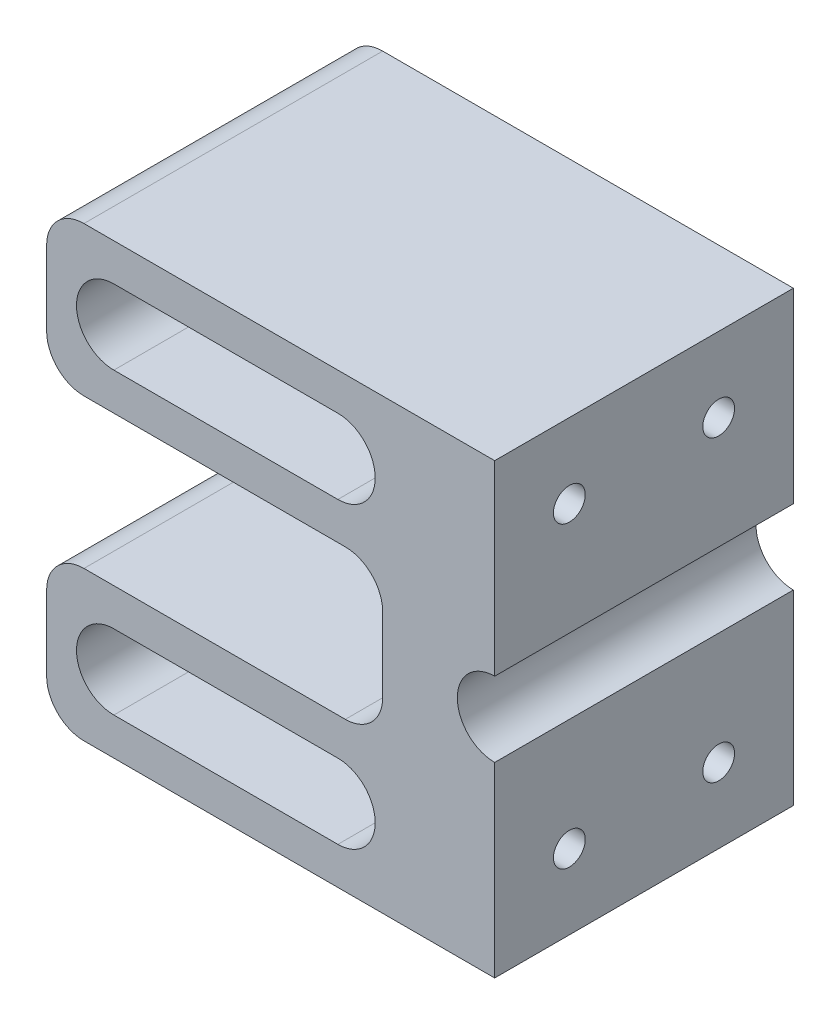
SolidWorks part; units mm, degrees
note: '?' marks a value the reader was unsure of.
ref_plane "Front Plane" through (0, 0, 0) normal (0, 0, 1) x (1, 0, 0)
ref_plane "Top Plane" through (0, 0, 0) normal (0, 1, 0) x (1, 0, 0)
ref_plane "Right Plane" through (0, 0, 0) normal (1, 0, 0) x (0, 0, -1)
sketch "Sketch1" plane through (0, 0, 0) normal (0, 0, 1) x (1, 0, 0)
  line L1 (-19.05, -12.7) -> (19.05, -12.7)
  line L2 (-19.05, -12.7) -> (-19.05, 12.7)
  line L3 (-19.05, 12.7) -> (19.05, 12.7)
  line L4 (19.05, -12.7) -> (19.05, 12.7)
  line L5 (-19.05, -12.7) -> (19.05, 12.7) construction
  line L6 (-19.05, 12.7) -> (19.05, -12.7) construction
  point P0 (0, 0)
  dimension "D1" = 38.1
  dimension "D2" = 25.4
extrude "Boss-Extrude1" add sketch "Sketch1" along normal mid plane 25.4
sketch "Sketch2" plane through (0, 0, 12.7) normal (0, 0, 1) x (1, 0, 0)
  line L0 (12.7, -5.08) -> (19.05, -5.08) construction
  line L1 (12.7, -1.905) -> (19.05, -1.905)
  line L2 (12.7, -8.255) -> (19.05, -8.255)
  line L3 (19.05, -12.7) -> (19.05, 12.7) construction
  line L4 (-19.05, -12.7) -> (19.05, -12.7) construction
  arc A0 (12.7, -1.905) -> (12.7, -8.255) centre (12.7, -5.08) ccw
  arc A1 (19.05, -8.255) -> (19.05, -1.905) centre (19.05, -5.08) ccw
  point P2 (15.875, -5.08)
  dimension "D1" = 6.35
  dimension "D2" = 6.35
  dimension "D3" = 7.62
extrude "Cut-Extrude1" [suppressed] cut sketch "Sketch2" against normal blind 25.4
sketch "Sketch3" plane through (0, 0, 12.7) normal (0, 0, 1) x (1, 0, 0)
  line L0 (0, -13.97) -> (0, 13.97) construction
  line L1 (19.05, 12.7) -> (-19.05, 12.7) construction
  point P0 (0, 6.35)
  dimension "D1" = 6.35
hole_wizard "1/4 (0.25) Diameter Hole1" [suppressed] positions "Sketch4" profile "Sketch6" hole size "1/4" standard "ANSI Inch"
sketch "Sketch4" plane through (0, 0, 12.7) normal (0, 0, 1) x (1, 0, 0)
  point P0 (0, 6.35)
sketch "Sketch6" plane through (0, 6.35, 12.7) normal (1, 0, 0) x (0, -1, 0)
  line L0 (0, 0) -> (0, 25.4)
  line L1 (0, 25.4) -> (3.175, 25.4)
  line L2 (3.175, 25.4) -> (3.175, 0)
  line L5 (3.175, 0) -> (0, 0)
  line L11 (0, -6.35) -> (0, 107.95) construction
  dimension "Thru Hole Dia." = 6.35
  dimension "Thru Hole Depth" = 25.4
sketch "Sketch7" plane through (0, 0, 12.7) normal (0, 0, 1) x (1, 0, 0)
  line L0 (19.05, -12.7) -> (19.05, 12.7) construction
  line L1 (-19.05, -12.7) -> (19.05, -12.7) construction
  circle A0 centre (19.05, -6.35) radius 3.175
  dimension "D1" = 6.35
  dimension "D2" = 6.35
extrude "Cut-Extrude2" cut sketch "Sketch7" against normal up to next
sketch "Sketch8" plane through (19.05, 0, 0) normal (1, 0, 0) x (0, 0, -1)
  line L0 (-6.35, 6.35) -> (6.35, 6.35) construction
  line L1 (0, 13.97) -> (0, -13.97) construction
  line L2 (-12.7, 12.7) -> (12.7, 12.7) construction
  point P0 (-6.35, 6.35)
  point P1 (6.35, 6.35)
  point P4 (0, 6.35)
  dimension "D1" = 12.7
  dimension "D2" = 6.35
hole_wizard "#6-32 Tapped Hole1" positions "Sketch9" profile "Sketch11" tap size "#6-32" standard "ANSI Inch"
sketch "Sketch9" plane through (19.05, 0, 0) normal (1, 0, 0) x (0, 0, -1)
  point P0 (-6.35, 6.35)
  point P3 (6.35, 6.35)
sketch "Sketch11" plane through (19.05, 6.35, 6.35) normal (0, 1, 0) x (0, 0, -1)
  line L0 (0, 0) -> (0, 8.89)
  line L1 (0, 8.89) -> (1.3525, 8.0773)
  line L2 (1.3525, 8.0773) -> (1.3525, 0)
  line L5 (1.3525, 0) -> (0, 0)
  line L10 (0, 8.89) -> (-1.3526, 8.0773) construction
  line L11 (0, -6.35) -> (0, 107.95) construction
  dimension "Tap Drill Dia." = 2.7051
  dimension "Tap Drill Depth" = 8.89
  dimension "Drill Angle" = 118
cosmetic thread "Hole Thread1" parameters "D1"=7.112, "D2"=3.5052
cosmetic thread "Hole Thread2" parameters "D1"=7.112, "D2"=3.5052
sketch "Sketch12" plane through (0, 0, 12.7) normal (0, 0, 1) x (1, 0, 0)
  line L0 (-13.335, 6.35) -> (5.715, 6.35) construction
  line L1 (-13.335, 9.525) -> (5.715, 9.525)
  line L2 (-13.335, 3.175) -> (5.715, 3.175)
  line L3 (19.05, 12.7) -> (-19.05, 12.7) construction
  line L4 (0, -13.97) -> (0, 13.97) construction
  arc A0 (-13.335, 9.525) -> (-13.335, 3.175) centre (-13.335, 6.35) ccw
  arc A1 (5.715, 3.175) -> (5.715, 9.525) centre (5.715, 6.35) ccw
  point P2 (-3.81, 6.35)
  dimension "D1" = 6.35
  dimension "D2" = 6.35
  dimension "D3" = 19.05
  dimension "D4" = 3.81
extrude "Cut-Extrude3" cut sketch "Sketch12" against normal blind 25.4
sketch "Sketch13" [suppressed] plane through (0, 0, 12.7) normal (0, 0, 1) x (1, 0, 0)
  line L0 (-7.62, 12.7) -> (-19.05, 12.7)
  line L1 (19.05, 12.7) -> (-19.05, 12.7) construction
  line L2 (-19.05, 12.7) -> (-19.05, -12.7)
  line L3 (-19.05, -12.7) -> (9.525, -12.7)
  line L4 (-19.05, -12.7) -> (19.05, -12.7) construction
  line L5 (9.525, -12.7) -> (9.525, 0)
  line L6 (13.97, 0) -> (-13.97, 0) construction
  line L7 (9.525, 0) -> (-7.62, 0)
  line L8 (-7.62, 0) -> (-7.62, 12.7)
  arc A0 (19.05, -3.175) -> (19.05, -9.525) centre (19.05, -6.35) ccw construction
  point P18 (15.875, -6.35)
  dimension "D1" = 6.35
  dimension "D2" = 11.43
extrude "Cut-Extrude4" [suppressed] cut sketch "Sketch13" against normal blind 25.4
sketch "Sketch14" plane through (0, 0, 12.7) normal (0, 0, 1) x (1, 0, 0)
  line L0 (13.97, 0) -> (-13.97, 0) construction
  line L1 (-19.05, -12.7) -> (9.525, -12.7)
  line L2 (-19.05, -12.7) -> (-19.05, 0)
  line L3 (-19.05, 0) -> (9.525, 0)
  line L4 (9.525, -12.7) -> (9.525, 0)
  arc A0 (19.05, -3.175) -> (19.05, -9.525) centre (19.05, -6.35) ccw construction
  point P10 (15.875, -6.35)
  dimension "D1" = 6.35
extrude "Cut-Extrude5" cut sketch "Sketch14" against normal blind 25.4
fillet "Fillet1" [suppressed] radius 2.54
fillet "Fillet2" radius 3.175 3 edges at (9.525, 0, 0) (-19.05, 0, 0) (-19.05, 12.7, 0)
ref_point "Point1"
ref_plane "Plane1" through (0, -6.35, 0) normal (0, 1, 0) x (1, 0, 0)
mirror "Mirror1" about plane through (0, -6.35, 0) normal (0, 1, 0) of "Fillet2", "Cut-Extrude5", "Cut-Extrude3", "#6-32 Tapped Hole1", "Cut-Extrude2", "Boss-Extrude1"
cosmetic thread "Hole Thread3" parameters "D1"=7.112, "D2"=3.5052
cosmetic thread "Hole Thread4" parameters "D1"=7.112, "D2"=3.5052
ref_axis "Axis1" [suppressed] through (19.05, -6.35, -12.7) along (0, 0, 1)?
ref_plane "Plane2" [suppressed] through (0, -6.35, 0) normal (0, 1, 0) x (1, 0, 0)
mirror "Mirror4" [suppressed] about plane through (0, -6.35, 0) normal (0, 1, 0)
fillet "Fillet3" radius 3.175 1 edges at (9.525, 0, 0)
